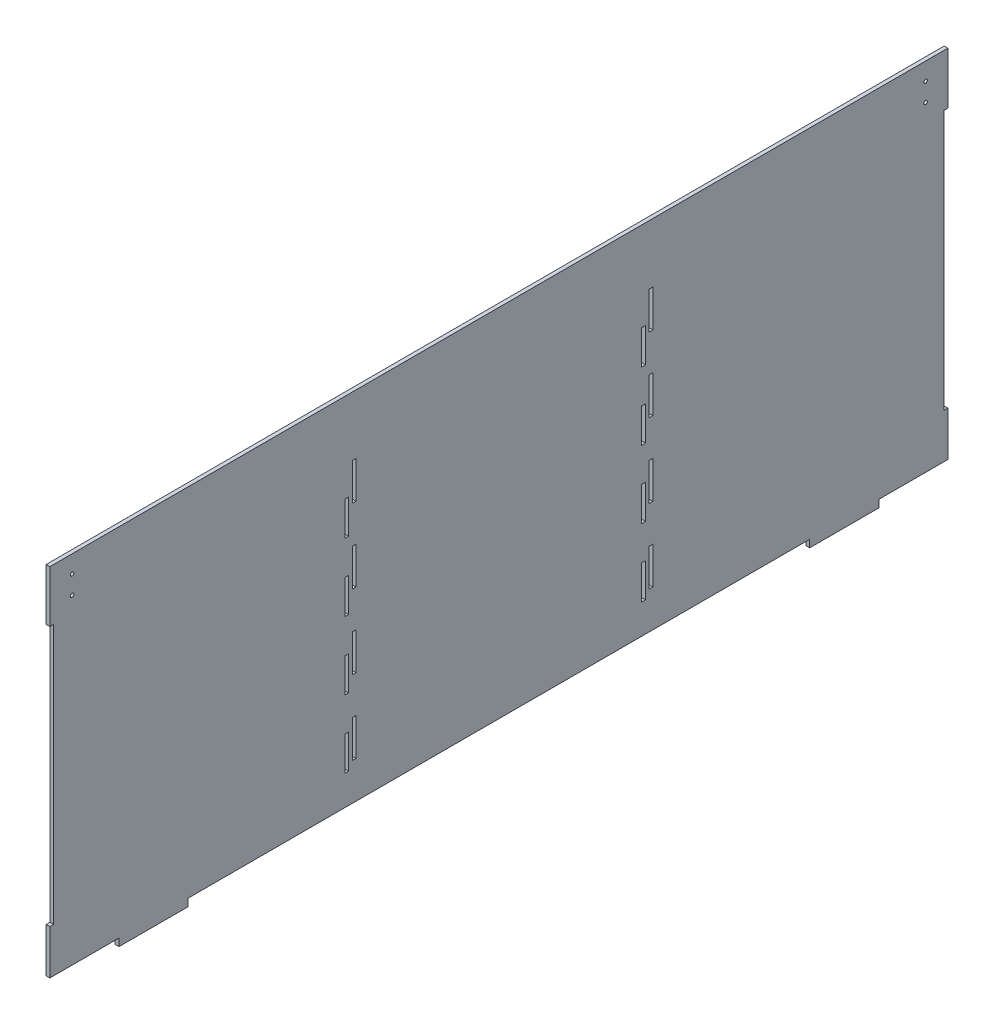
SolidWorks part; units mm, degrees
material "Acrylic (Medium-high impact)"
ref_plane "Front Plane" through (0, 0, 0) normal (0, 0, 1) x (1, 0, 0)
ref_plane "Top Plane" through (0, 0, 0) normal (0, 1, 0) x (1, 0, 0)
ref_plane "Right Plane" through (0, 0, 0) normal (1, 0, 0) x (0, 0, -1)
sketch "Sketch1" plane through (0, 0, 0) normal (1, 0, 0) x (0, 0, -1)
  line L0 (0, 152.4) -> (0, -152.4) construction
  line L1 (-381, 152.4) -> (381, 152.4)
  line L2 (-381, 152.4) -> (-381, -152.4)
  line L3 (-381, -152.4) -> (381, -152.4)
  line L4 (381, 152.4) -> (381, -152.4)
  line L5 (-381, 107.95) -> (-381, 63.5)
  line L10 (-381, 152.4) -> (-384.175, 152.4)
  line L11 (-381, 152.4) -> (-381, 107.95)
  line L12 (-381, 107.95) -> (-384.175, 107.95)
  line L13 (-384.175, 152.4) -> (-384.175, 107.95)
  line L14 (381, 152.4) -> (384.175, 152.4)
  line L15 (381, 152.4) -> (381, 107.95)
  line L16 (381, 107.95) -> (384.175, 107.95)
  line L17 (384.175, 152.4) -> (384.175, 107.95)
  line L18 (-384.175, -152.4) -> (-325.0712, -152.4)
  line L19 (-384.175, -152.4) -> (-384.175, -158.75)
  line L20 (-384.175, -158.75) -> (-325.0712, -158.75)
  line L21 (-325.0712, -152.4) -> (-325.0712, -158.75)
  line L22 (-381, 107.95) -> (-384.175, 107.95)
  line L23 (-384.175, 107.95) -> (-384.175, 63.5)
  line L24 (-381, 63.5) -> (-384.175, 63.5)
  line L25 (381, 107.95) -> (381, 63.5)
  line L26 (381, 107.95) -> (384.175, 107.95)
  line L27 (384.175, 107.95) -> (384.175, 63.5)
  line L28 (381, 63.5) -> (384.175, 63.5)
  line L29 (-381, 63.5) -> (-381, 19.05)
  line L30 (-381, 63.5) -> (-384.175, 63.5)
  line L31 (-384.175, 63.5) -> (-384.175, 19.05)
  line L32 (-381, 19.05) -> (-384.175, 19.05)
  line L33 (381, 63.5) -> (381, 19.05)
  line L34 (381, 63.5) -> (384.175, 63.5)
  line L35 (384.175, 63.5) -> (384.175, 19.05)
  line L36 (381, 19.05) -> (384.175, 19.05)
  line L37 (-381, 19.05) -> (-381, -25.4)
  line L38 (-381, 19.05) -> (-384.175, 19.05)
  line L39 (-384.175, 19.05) -> (-384.175, -25.4)
  line L40 (-381, -25.4) -> (-384.175, -25.4)
  line L41 (381, 19.05) -> (381, -25.4)
  line L42 (381, 19.05) -> (384.175, 19.05)
  line L43 (384.175, 19.05) -> (384.175, -25.4)
  line L44 (381, -25.4) -> (384.175, -25.4)
  line L45 (-381, -25.4) -> (-381, -69.85)
  line L46 (-381, -25.4) -> (-384.175, -25.4)
  line L47 (-384.175, -25.4) -> (-384.175, -69.85)
  line L48 (-381, -69.85) -> (-384.175, -69.85)
  line L49 (381, -25.4) -> (381, -69.85)
  line L50 (381, -25.4) -> (384.175, -25.4)
  line L51 (384.175, -25.4) -> (384.175, -69.85)
  line L52 (381, -69.85) -> (384.175, -69.85)
  line L53 (-381, -69.85) -> (-381, -114.3)
  line L54 (-381, -69.85) -> (-384.175, -69.85)
  line L55 (-384.175, -69.85) -> (-384.175, -114.3)
  line L56 (-381, -114.3) -> (-384.175, -114.3)
  line L57 (381, -69.85) -> (381, -114.3)
  line L58 (381, -69.85) -> (384.175, -69.85)
  line L59 (384.175, -69.85) -> (384.175, -114.3)
  line L60 (381, -114.3) -> (384.175, -114.3)
  line L61 (-381, -114.3) -> (-381, -158.75)
  line L62 (-381, -114.3) -> (-384.175, -114.3)
  line L63 (-384.175, -114.3) -> (-384.175, -158.75)
  line L64 (-381, -158.75) -> (-384.175, -158.75)
  line L65 (381, -114.3) -> (381, -158.75)
  line L66 (381, -114.3) -> (384.175, -114.3)
  line L67 (384.175, -114.3) -> (384.175, -158.75)
  line L68 (381, -158.75) -> (384.175, -158.75)
  line L69 (-325.0712, -158.75) -> (-265.9673, -158.75)
  line L70 (-325.0712, -152.4) -> (-325.0712, -158.75)
  line L71 (-325.0712, -152.4) -> (-265.9673, -152.4)
  line L72 (-265.9673, -152.4) -> (-265.9673, -158.75)
  line L73 (-265.9673, -158.75) -> (-206.8635, -158.75)
  line L74 (-265.9673, -152.4) -> (-265.9673, -158.75)
  line L75 (-265.9673, -152.4) -> (-206.8635, -152.4)
  line L76 (-206.8635, -152.4) -> (-206.8635, -158.75)
  line L77 (-206.8635, -158.75) -> (-147.7596, -158.75)
  line L78 (-206.8635, -152.4) -> (-206.8635, -158.75)
  line L79 (-206.8635, -152.4) -> (-147.7596, -152.4)
  line L80 (-147.7596, -152.4) -> (-147.7596, -158.75)
  line L81 (-147.7596, -158.75) -> (-88.6558, -158.75)
  line L82 (-147.7596, -152.4) -> (-147.7596, -158.75)
  line L83 (-147.7596, -152.4) -> (-88.6558, -152.4)
  line L84 (-88.6558, -152.4) -> (-88.6558, -158.75)
  line L85 (-88.6558, -158.75) -> (-29.5519, -158.75)
  line L86 (-88.6558, -152.4) -> (-88.6558, -158.75)
  line L87 (-88.6558, -152.4) -> (-29.5519, -152.4)
  line L88 (-29.5519, -152.4) -> (-29.5519, -158.75)
  line L89 (-29.5519, -158.75) -> (29.5519, -158.75)
  line L90 (-29.5519, -152.4) -> (-29.5519, -158.75)
  line L91 (-29.5519, -152.4) -> (29.5519, -152.4)
  line L92 (29.5519, -152.4) -> (29.5519, -158.75)
  line L93 (29.5519, -158.75) -> (88.6558, -158.75)
  line L94 (29.5519, -152.4) -> (29.5519, -158.75)
  line L95 (29.5519, -152.4) -> (88.6558, -152.4)
  line L96 (88.6558, -152.4) -> (88.6558, -158.75)
  line L97 (88.6558, -158.75) -> (147.7596, -158.75)
  line L98 (88.6558, -152.4) -> (88.6558, -158.75)
  line L99 (88.6558, -152.4) -> (147.7596, -152.4)
  line L100 (147.7596, -152.4) -> (147.7596, -158.75)
  line L101 (147.7596, -158.75) -> (206.8635, -158.75)
  line L102 (147.7596, -152.4) -> (147.7596, -158.75)
  line L103 (147.7596, -152.4) -> (206.8635, -152.4)
  line L104 (206.8635, -152.4) -> (206.8635, -158.75)
  line L105 (206.8635, -158.75) -> (265.9673, -158.75)
  line L106 (206.8635, -152.4) -> (206.8635, -158.75)
  line L107 (206.8635, -152.4) -> (265.9673, -152.4)
  line L108 (265.9673, -152.4) -> (265.9673, -158.75)
  line L125 (-125.4125, 0) -> (125.4125, 0) construction
  line L126 (-128.5875, 41.956) -> (-125.4125, 41.956) construction
  line L127 (-128.5875, 41.956) -> (-128.5875, -41.956) construction
  line L128 (-128.5875, -41.956) -> (-125.4125, -41.956) construction
  line L129 (-125.4125, 41.956) -> (-125.4125, -41.956) construction
  line L138 (125.4125, 41.956) -> (128.5875, 41.956) construction
  line L139 (125.4125, 41.956) -> (125.4125, -41.956) construction
  line L140 (125.4125, -41.956) -> (128.5875, -41.956) construction
  line L141 (128.5875, 41.956) -> (128.5875, -41.956) construction
  line L143 (265.9673, -158.75) -> (325.0712, -158.75)
  line L144 (265.9673, -152.4) -> (265.9673, -158.75)
  line L145 (265.9673, -152.4) -> (325.0712, -152.4)
  line L146 (325.0712, -152.4) -> (325.0712, -158.75)
  line L147 (325.0712, -158.75) -> (384.175, -158.75)
  line L148 (325.0712, -152.4) -> (325.0712, -158.75)
  line L149 (325.0712, -152.4) -> (384.175, -152.4)
  line L150 (384.175, -152.4) -> (384.175, -158.75)
  point P6 (0, 0)
  point P113 (-127, 41.956)
  point P114 (127, 41.956)
  point P117 (0, 0)
  dimension "D1" = 762
  dimension "D2" = 304.8
  dimension "D3" = 768.35
  dimension "D4" = 311.15
  dimension "D5" = 44.45
  dimension "D7" = 59.1038
  dimension "D9" = 254
  dimension "D10" = 3.175
  dimension "D6" = 7
  dimension "D8" = 13
extrude "Boss-Extrude1" add sketch "Sketch1" along normal blind 3.175 contours L0 L1 L2 L3 | L10 L13 L12 L2 | L56 L63 L18 L2 | L72 L3 L21 L69 | L3 L108 | L4 L67 L60 | L17 L14 L4 L16 | L29 L32 L31 L30 | L45 L48 L47 L46 | L77 L80 L79 L78 | L85 L88 L87 L86 | L93 L96 L95 L94 | L101 L104 L103 L102 | L49 L52 L51 L50 | L33 L36 L35 L34 region at (0, 0, 0) region at (0, 130.175, 382.5875) region at (0, 130.175, -382.5875) region at (0, -133.35, 382.5875) region at (0, -133.35, -382.5875) region at (0, -155.575, 295.5192) region at (0, -155.575, -295.5192)
sketch "Sketch3" plane through (3.175, 0, 0) normal (1, 0, 0) x (0, 0, -1)
  line L0 (-128.5887, -127) -> (-128.5887, 76.2) construction
  line L5 (-131.7637, 76.2) -> (-128.5887, 76.2)
  line L6 (-131.7637, 76.2) -> (-131.7637, 47.1714)
  line L7 (-131.7637, 47.1714) -> (-128.5887, 47.1714)
  line L8 (-128.5887, 76.2) -> (-128.5887, 47.1714)
  line L9 (-122.2363, 101.6) -> (-125.4113, 101.6)
  line L10 (-122.2363, 101.6) -> (-122.2363, 69.85)
  line L11 (-122.2363, 69.85) -> (-125.4113, 69.85)
  line L12 (-125.4113, 101.6) -> (-125.4113, 69.85)
  line L13 (-381, -152.4) -> (381, -152.4) construction
  line L14 (-125.4113, -152.4) -> (-125.4113, 101.6) construction
  line L15 (-128.5887, 76.2) -> (-125.4113, 76.2) construction
  line L16 (-127, 41.956) -> (-127, 76.2) construction
  line L17 (-128.5875, 41.956) -> (-125.4125, 41.956) construction
  line L18 (-122.2363, 69.85) -> (-122.2363, 38.1)
  line L19 (-122.2363, 69.85) -> (-125.4113, 69.85)
  line L20 (-125.4113, 69.85) -> (-125.4113, 38.1)
  line L21 (-122.2363, 38.1) -> (-125.4113, 38.1)
  line L22 (-122.2363, 38.1) -> (-122.2363, 6.35)
  line L23 (-122.2363, 38.1) -> (-125.4113, 38.1)
  line L24 (-125.4113, 38.1) -> (-125.4113, 6.35)
  line L25 (-122.2363, 6.35) -> (-125.4113, 6.35)
  line L26 (-122.2363, 6.35) -> (-122.2363, -25.4)
  line L27 (-122.2363, 6.35) -> (-125.4113, 6.35)
  line L28 (-125.4113, 6.35) -> (-125.4113, -25.4)
  line L29 (-122.2363, -25.4) -> (-125.4113, -25.4)
  line L30 (-122.2363, -25.4) -> (-122.2363, -57.15)
  line L31 (-122.2363, -25.4) -> (-125.4113, -25.4)
  line L32 (-125.4113, -25.4) -> (-125.4113, -57.15)
  line L33 (-122.2363, -57.15) -> (-125.4113, -57.15)
  line L34 (-122.2363, -57.15) -> (-122.2363, -88.9)
  line L35 (-122.2363, -57.15) -> (-125.4113, -57.15)
  line L36 (-125.4113, -57.15) -> (-125.4113, -88.9)
  line L37 (-122.2363, -88.9) -> (-125.4113, -88.9)
  line L38 (-122.2363, -88.9) -> (-122.2363, -120.65)
  line L39 (-122.2363, -88.9) -> (-125.4113, -88.9)
  line L40 (-125.4113, -88.9) -> (-125.4113, -120.65)
  line L41 (-122.2363, -120.65) -> (-125.4113, -120.65)
  line L42 (-131.7637, 47.1714) -> (-131.7637, 18.1429)
  line L43 (-131.7637, 47.1714) -> (-128.5887, 47.1714)
  line L44 (-128.5887, 47.1714) -> (-128.5887, 18.1429)
  line L45 (-131.7637, 18.1429) -> (-128.5887, 18.1429)
  line L46 (-131.7637, 18.1429) -> (-131.7637, -10.8857)
  line L47 (-131.7637, 18.1429) -> (-128.5887, 18.1429)
  line L48 (-128.5887, 18.1429) -> (-128.5887, -10.8857)
  line L49 (-131.7637, -10.8857) -> (-128.5887, -10.8857)
  line L50 (-131.7637, -10.8857) -> (-131.7637, -39.9143)
  line L51 (-131.7637, -10.8857) -> (-128.5887, -10.8857)
  line L52 (-128.5887, -10.8857) -> (-128.5887, -39.9143)
  line L53 (-131.7637, -39.9143) -> (-128.5887, -39.9143)
  line L54 (-131.7637, -39.9143) -> (-131.7637, -68.9429)
  line L55 (-131.7637, -39.9143) -> (-128.5887, -39.9143)
  line L56 (-128.5887, -39.9143) -> (-128.5887, -68.9429)
  line L57 (-131.7637, -68.9429) -> (-128.5887, -68.9429)
  line L58 (-131.7637, -68.9429) -> (-131.7637, -97.9714)
  line L59 (-131.7637, -68.9429) -> (-128.5887, -68.9429)
  line L60 (-128.5887, -68.9429) -> (-128.5887, -97.9714)
  line L61 (-131.7637, -97.9714) -> (-128.5887, -97.9714)
  line L62 (-131.7637, -97.9714) -> (-131.7637, -127)
  line L63 (-131.7637, -97.9714) -> (-128.5887, -97.9714)
  line L64 (-128.5887, -97.9714) -> (-128.5887, -127)
  line L65 (-131.7637, -127) -> (-128.5887, -127)
  line L66 (-122.2363, -120.65) -> (-122.2363, -152.4)
  line L67 (-122.2363, -120.65) -> (-125.4113, -120.65)
  line L68 (-125.4113, -120.65) -> (-125.4113, -152.4)
  line L69 (-122.2363, -152.4) -> (-125.4113, -152.4)
  line L70 (122.2363, 76.2) -> (125.4113, 76.2)
  line L71 (122.2363, 76.2) -> (122.2363, 47.1714)
  line L72 (122.2363, 47.1714) -> (125.4113, 47.1714)
  line L73 (125.4113, 76.2) -> (125.4113, 47.1714)
  line L74 (131.7637, 101.6) -> (128.5887, 101.6)
  line L75 (131.7637, 101.6) -> (131.7637, 69.85)
  line L76 (131.7637, 69.85) -> (128.5887, 69.85)
  line L77 (128.5887, 101.6) -> (128.5887, 69.85)
  line L78 (131.7637, 69.85) -> (131.7637, 38.1)
  line L79 (131.7637, 69.85) -> (128.5887, 69.85)
  line L80 (128.5887, 69.85) -> (128.5887, 38.1)
  line L81 (131.7637, 38.1) -> (128.5887, 38.1)
  line L82 (131.7637, 38.1) -> (131.7637, 6.35)
  line L83 (131.7637, 38.1) -> (128.5887, 38.1)
  line L84 (128.5887, 38.1) -> (128.5887, 6.35)
  line L85 (131.7637, 6.35) -> (128.5887, 6.35)
  line L86 (131.7637, 6.35) -> (131.7637, -25.4)
  line L87 (131.7637, 6.35) -> (128.5887, 6.35)
  line L88 (128.5887, 6.35) -> (128.5887, -25.4)
  line L89 (131.7637, -25.4) -> (128.5887, -25.4)
  line L90 (131.7637, -25.4) -> (131.7637, -57.15)
  line L91 (131.7637, -25.4) -> (128.5887, -25.4)
  line L92 (128.5887, -25.4) -> (128.5887, -57.15)
  line L93 (131.7637, -57.15) -> (128.5887, -57.15)
  line L94 (131.7637, -57.15) -> (131.7637, -88.9)
  line L95 (131.7637, -57.15) -> (128.5887, -57.15)
  line L96 (128.5887, -57.15) -> (128.5887, -88.9)
  line L97 (131.7637, -88.9) -> (128.5887, -88.9)
  line L98 (131.7637, -88.9) -> (131.7637, -120.65)
  line L99 (131.7637, -88.9) -> (128.5887, -88.9)
  line L100 (128.5887, -88.9) -> (128.5887, -120.65)
  line L101 (131.7637, -120.65) -> (128.5887, -120.65)
  line L102 (122.2363, 47.1714) -> (122.2363, 18.1429)
  line L103 (122.2363, 47.1714) -> (125.4113, 47.1714)
  line L104 (125.4113, 47.1714) -> (125.4113, 18.1429)
  line L105 (122.2363, 18.1429) -> (125.4113, 18.1429)
  line L106 (122.2363, 18.1429) -> (122.2363, -10.8857)
  line L107 (122.2363, 18.1429) -> (125.4113, 18.1429)
  line L108 (125.4113, 18.1429) -> (125.4113, -10.8857)
  line L109 (122.2363, -10.8857) -> (125.4113, -10.8857)
  line L110 (122.2363, -10.8857) -> (122.2363, -39.9143)
  line L111 (122.2363, -10.8857) -> (125.4113, -10.8857)
  line L112 (125.4113, -10.8857) -> (125.4113, -39.9143)
  line L113 (122.2363, -39.9143) -> (125.4113, -39.9143)
  line L114 (122.2363, -39.9143) -> (122.2363, -68.9429)
  line L115 (122.2363, -39.9143) -> (125.4113, -39.9143)
  line L116 (125.4113, -39.9143) -> (125.4113, -68.9429)
  line L117 (122.2363, -68.9429) -> (125.4113, -68.9429)
  line L118 (122.2363, -68.9429) -> (122.2363, -97.9714)
  line L119 (122.2363, -68.9429) -> (125.4113, -68.9429)
  line L120 (125.4113, -68.9429) -> (125.4113, -97.9714)
  line L121 (122.2363, -97.9714) -> (125.4113, -97.9714)
  line L122 (122.2363, -97.9714) -> (122.2363, -127)
  line L123 (122.2363, -97.9714) -> (125.4113, -97.9714)
  line L124 (125.4113, -97.9714) -> (125.4113, -127)
  line L125 (122.2363, -127) -> (125.4113, -127)
  line L126 (131.7637, -120.65) -> (131.7637, -152.4)
  line L127 (131.7637, -120.65) -> (128.5887, -120.65)
  line L128 (128.5887, -120.65) -> (128.5887, -152.4)
  line L129 (131.7637, -152.4) -> (128.5887, -152.4)
  line L130 (125.4113, -127) -> (125.4113, 76.2) construction
  line L131 (128.5887, -152.4) -> (128.5887, 101.6) construction
  line L132 (125.4113, 76.2) -> (128.5887, 76.2) construction
  line L133 (127, 41.956) -> (127, 76.2) construction
  line L134 (125.4125, 41.956) -> (128.5875, 41.956) construction
  dimension "D1" = 203.2
  dimension "D2" = 254
  dimension "D3" = 25.4
  dimension "D4" = 3.1775
  dimension "D5" = 3.175
  dimension "D7" = 31.75
  dimension "D9" = 29.0286
  dimension "D6" = 8
  dimension "D8" = 7
  dimension "D10" = 2
extrude "Cut-Extrude1" cut sketch "Sketch3" against normal through all contours L41 L38 L37 L40 | L33 L30 L29 L32 | L25 L22 L21 L24 | L9 L12 L11 L10 | L8 L5 L6 L7 | L46 L49 L48 L45 | L54 L57 L56 L53 | L62 L65 L64 L61 | L74 L77 L76 L75 | L73 L70 L71 L72 | L85 L82 L81 L84 | L106 L109 L108 L105 | L93 L90 L89 L92 | L114 L117 L116 L113 | L101 L98 L97 L100 | L122 L125 L124 L121 region at (3.175, 61.6857, 130.1762) region at (3.175, 3.6286, 130.1762) region at (3.175, -54.4286, 130.1762) region at (3.175, -112.4857, 130.1762) region at (3.175, 85.725, 123.8238) region at (3.175, 22.225, 123.8238) region at (3.175, -41.275, 123.8238) region at (3.175, -104.775, 123.8238) region at (3.175, 61.6857, -123.8238) region at (3.175, 3.6286, -123.8238) region at (3.175, -54.4286, -123.8238) region at (3.175, -112.4857, -123.8238) region at (3.175, 85.725, -130.1762) region at (3.175, 22.225, -130.1762) region at (3.175, -41.275, -130.1762) region at (3.175, -104.775, -130.1762)
sketch "Sketch4" plane through (3.175, 0, 0) normal (1, 0, 0) x (0, 0, -1)
  line L0 (0, 152.4) -> (0, -152.4) construction
  line L1 (-384.175, 152.4) -> (384.175, 152.4) construction
  line L5 (-384.175, 152.4) -> (-384.175, 107.95) construction
  circle A0 centre (-365.125, 137.4) radius 1.5
  circle A1 centre (-365.125, 121.65) radius 1.5
  circle A2 centre (365.125, 137.4) radius 1.5
  circle A3 centre (365.125, 121.65) radius 1.5
  dimension "D1" = 3
  dimension "D2" = 3
  dimension "D3" = 19.05
  dimension "D4" = 15.75
  dimension "D5" = 15
extrude "Cut-Extrude2" cut sketch "Sketch4" against normal up to surface (3.175 mm away) up to face at (0, 3.6286, 130.1762)
sketch "Sketch5" plane through (3.175, 0, 0) normal (1, 0, 0) x (0, 0, -1)
  line L0 (-384.175, 63.5) -> (-381, 63.5)
  line L1 (-381, 63.5) -> (-381, 19.05)
  line L2 (-381, 19.05) -> (-384.175, 19.05)
  line L3 (-384.175, 19.05) -> (-384.175, 63.5)
  line L4 (-384.175, -25.4) -> (-381, -25.4)
  line L5 (-381, -25.4) -> (-381, -69.85)
  line L6 (-381, -69.85) -> (-384.175, -69.85)
  line L7 (-384.175, -69.85) -> (-384.175, -25.4)
  line L9 (-206.8635, -152.4) -> (-147.7596, -152.4)
  line L10 (-206.8635, -152.4) -> (-206.8635, -158.75)
  line L11 (-206.8635, -158.75) -> (-147.7596, -158.75)
  line L12 (-147.7596, -152.4) -> (-147.7596, -158.75)
  line L13 (-88.6558, -152.4) -> (-29.5519, -152.4)
  line L14 (-88.6558, -152.4) -> (-88.6558, -158.75)
  line L15 (-88.6558, -158.75) -> (-29.5519, -158.75)
  line L16 (-29.5519, -152.4) -> (-29.5519, -158.75)
  line L17 (29.5519, -152.4) -> (88.6558, -152.4)
  line L18 (29.5519, -152.4) -> (29.5519, -158.75)
  line L19 (29.5519, -158.75) -> (88.6558, -158.75)
  line L20 (88.6558, -152.4) -> (88.6558, -158.75)
  line L21 (147.7596, -152.4) -> (206.8635, -152.4)
  line L22 (147.7596, -152.4) -> (147.7596, -158.75)
  line L23 (147.7596, -158.75) -> (206.8635, -158.75)
  line L24 (206.8635, -152.4) -> (206.8635, -158.75)
  line L25 (384.175, -69.85) -> (381, -69.85)
  line L26 (384.175, -69.85) -> (384.175, -25.4)
  line L27 (384.175, -25.4) -> (381, -25.4)
  line L28 (381, -69.85) -> (381, -25.4)
  line L29 (384.175, 19.05) -> (381, 19.05)
  line L30 (384.175, 19.05) -> (384.175, 63.5)
  line L31 (384.175, 63.5) -> (381, 63.5)
  line L32 (381, 19.05) -> (381, 63.5)
extrude "Cut-Extrude3" cut sketch "Sketch5" against normal up to surface (3.175 mm away) up to face at (0, 121.65, 363.625)
equation "\"Height\"= 12in"
equation "\"Depth\"= 7in"
equation "\"WallThickness\"= 0.125in"
equation "\"FloorThickness\"= 0.25in"
equation "\"D2@Sketch1\"=\"Height\""
equation "\"D3@Sketch1\"=\"D1@Sketch1\"+2*\"WallThickness\""
equation "\"D4@Sketch1\"=\"D2@Sketch1\"+\"FloorThickness\""
equation "\"D5@Sketch1\"=\"D4@Sketch1\"/7"
equation "\"D7@Sketch1\"=\"D3@Sketch1\"/\"D8@Sketch1\""
equation "\"D1@Boss-Extrude1\"=\"WallThickness\""
equation "\"Width\" = 30in"
equation "\"D4@Sketch3\"=\"WallThickness\"+(1/16in)"
equation "\"D5@Sketch3\"=\"WallThickness\""
equation "\"D7@Sketch3\"=\"D2@Sketch3\"/\"D6@Sketch3\""
equation "\"D9@Sketch3\"=\"D1@Sketch3\"/\"D8@Sketch3\""
equation "\"D10@Sketch1\"=\"WallThickness\""
equation "\"D1@Sketch1\"=\"Width\""
